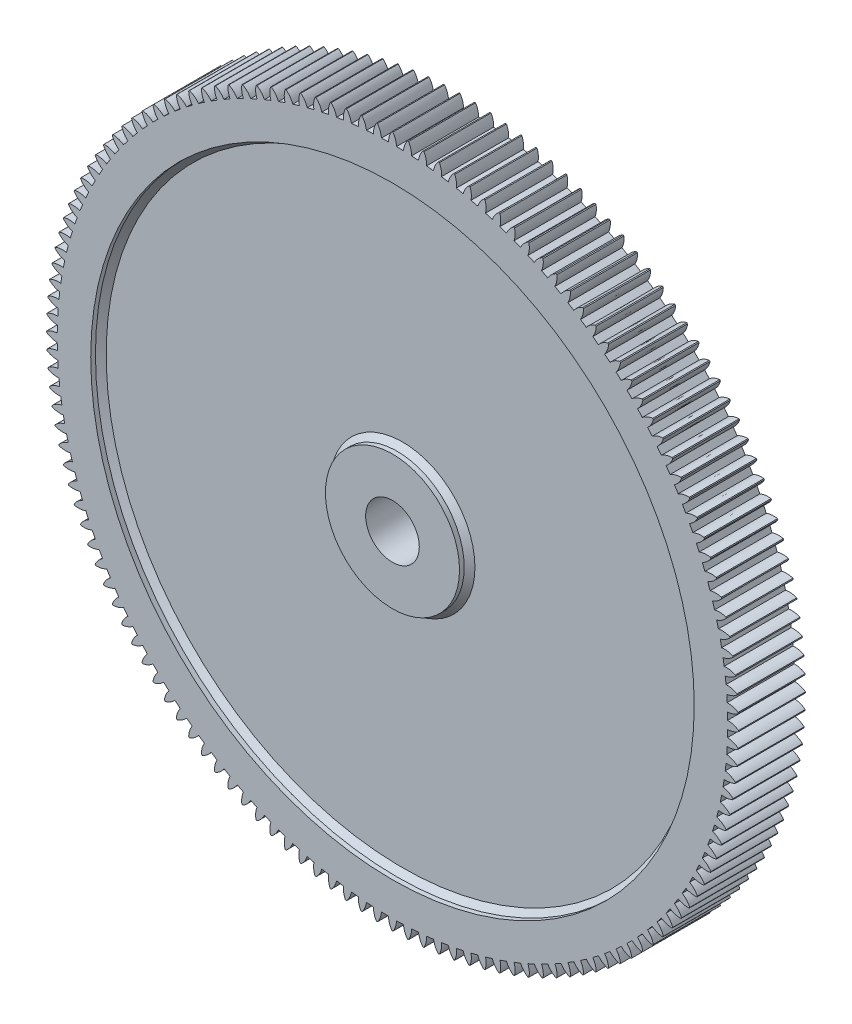
SolidWorks part; units mm, degrees
material "Cast iron, gray, flake graphite, EN GJL 250"
ref_plane "Front Plane" through (0, 0, 0) normal (0, 0, 1) x (1, 0, 0)
ref_plane "Top Plane" through (0, 0, 0) normal (0, 1, 0) x (1, 0, 0)
ref_plane "Right Plane" through (0, 0, 0) normal (1, 0, 0) x (0, 0, -1)
sketch "Sketch8" plane through (0, 0, 0) normal (0, 0, 1) x (1, 0, 0)
  circle A0 centre (0, 0) radius 225
  circle A1 centre (0, 0) radius 250
  dimension "D1" = 500
  dimension "D2" = 450
extrude "Boss-Extrude1" add sketch "Sketch8" along normal mid plane 50
sketch "Sketch9" plane through (0, 0, 0) normal (0, 0, 1) x (1, 0, 0)
  circle A0 centre (0, 0) radius 50
  dimension "D1" = 100
extrude "Boss-Extrude2" add sketch "Sketch9" along normal mid plane 50 separate body
sketch "Sketch10" plane through (0, 0, 0) normal (0, 0, 1) x (1, 0, 0)
  circle A0 centre (0, 0) radius 50
  circle A1 centre (0, 0) radius 225
  circle A2 centre (0, 0) radius 50 construction
  circle A3 centre (0, 0) radius 225 construction
extrude "Boss-Extrude3" add sketch "Sketch10" along normal mid plane 35
chamfer "Chamfer2" distance 4 angle 45 4 edges at (225, 0, 17.5) (50, 0, 17.5) (225, 0, -17.5) (50, 0, -17.5)
sketch "Sketch11" plane through (0, 0, 25) normal (0, 0, 1) x (1, 0, 0)
  circle A0 centre (0, 0) radius 20
  dimension "D1" = 40
extrude "Cut-Extrude1" cut sketch "Sketch11" against normal through all
ref_axis "Axis1" through (0, 0, -12.82) along (0, 0, 1)
sketch "Sketch13" plane through (0, 0, 25) normal (0, 0, 1) x (1, 0, 0)
  line L0 (-0.375, 258) -> (0.375, 258)
  line L1 (4.7384, 265.3027) -> (-5.4884, 250.6973) construction
  line L2 (0, 258) -> (0, 250) construction
  circle A0 centre (0, 0) radius 250 construction
  arc A1 (3, 249.982) -> (-3, 249.982) centre (0, 0) ccw
  spline S0 degree 2 poles (-3, 249.982) (-2.8086, 254.5245) (-0.375, 258) knots 0 0 0 0.951846 0.951846 0.951846
  spline S1 degree 2 poles (3, 249.982) (2.8086, 254.5245) (0.375, 258) knots 0 0 0 0.951846 0.951846 0.951846
  dimension "D1" = 55
  dimension "D3" = 8
  dimension "D4" = 6
  dimension "D5" = 8.4857
  dimension "D2" = 0.75
extrude "Boss-Extrude4" add sketch "Sketch13" against normal up to surface (50 mm away) up to face at (250, 0, -25)
pattern_circular "CirPattern2" count 140 over 360 about axis through (0, 0, 25) along (0, 0, -1) of "Boss-Extrude4"
equation "\"Flywheel Diameter\"= 500mm"
equation "\"Crankshaft Radius\"= 40mm"
equation "\"Flywheel Thickness\"= 50mm"
equation "\"D1@Sketch8\"=\"Flywheel Diameter\""
equation "\"D2@Sketch8\"=\"Flywheel Diameter\"-50mm"
equation "\"D1@Boss-Extrude1\"=\"Flywheel Thickness\""
equation "\"Hub Diameter\"= \"Crankshaft Radius\" + 60mm"
equation "\"D1@Sketch9\"=\"Hub Diameter\""
equation "\"D1@Boss-Extrude2\"=\"Flywheel Thickness\""
equation "\"D1@Boss-Extrude3\"=\"Flywheel Thickness\"*0.7"
equation "\"D1@Sketch11\"=\"Crankshaft Radius\""
